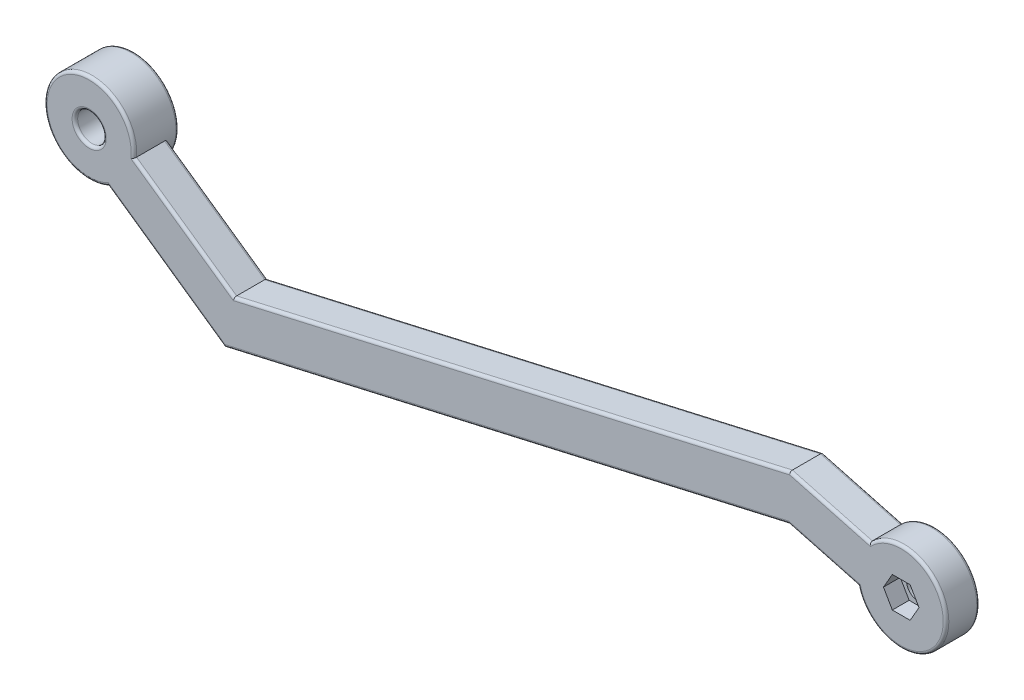
SolidWorks part; units mm, degrees
ref_plane "前视基准面" through (0, 0, 0) normal (0, 0, 1) x (1, 0, 0)
ref_plane "上视基准面" through (0, 0, 0) normal (0, 1, 0) x (1, 0, 0)
ref_plane "右视基准面" through (0, 0, 0) normal (1, 0, 0) x (0, 0, -1)
other "Configuration Table"
sketch "草图1" plane through (0, 0, 0) normal (0, 0, 1) x (1, 0, 0)
  line L0 (0, 0) -> (-145, 0) construction
  line L3 (-145, 0) -> (-120, -17.5052) construction
  line L4 (-120, -17.5052) -> (-20, 5.359) construction
  line L5 (-20, 5.359) -> (0, 0) construction
  line L7 (-142.7057, 3.2766) -> (-119.1604, -13.21)
  line L8 (-147.2943, -3.2766) -> (-120.8396, -21.8004)
  line L10 (-120.8396, -21.8004) -> (-20.0763, 1.2383)
  line L11 (-20.0763, 1.2383) -> (-1.0353, -3.8637)
  line L12 (1.0353, 3.8637) -> (-19.9237, 9.4796)
  line L13 (-19.9237, 9.4796) -> (-119.1604, -13.21)
  arc A0 (-5.6569, 5.6569) -> (-7.7274, -2.0706) centre (0, 0) cw
  arc A1 (-137.0304, -0.6972) -> (-141.6191, -7.2505) centre (-145, 0) ccw
  circle A2 centre (-145, 0) radius 4
  circle A3 centre (0, 0) radius 4
  circle A4 centre (-145, 0) radius 2.55
  circle A5 centre (0, 0) radius 2.05
  dimension "D2" = 8
  dimension "D3" = 8
  dimension "D6" = 5.1
  dimension "D7" = 4.1
  dimension "D1" = 145
  dimension "D4" = 25
  dimension "D5" = 35
  dimension "D8" = 15
  dimension "D9" = 20
  dimension "D10" = 4
  dimension "D11" = 4
extrude "凸台-拉伸1" add sketch "草图1" along normal mid plane 6 contours A2 A4 | A2 L7 A1 L8 | A3 L12 L13 L7 A2 L8 L10 L11 | A3 L11 A0 L12 | A3 A5 region at (-148.462, 2.4241, 0) region at (-74.4027, -5.6599, 0) region at (-141.5523, 1.7948, 0) region at (7.5107, -2.0125, 0) region at (3.0837, 2.3662, 0)
ref_axis "后基准轴" through (0, 0, 0) along (0, 0, 1)
ref_axis "前基准轴" through (-145, 0, 0) along (0, 0, 1)
sketch "草图2" plane through (0, 0, -3) normal (0, 0, 1) x (1, 0, 0)
  circle A0 centre (-145, 0) radius 2.55
  circle A1 centre (-145, 0) radius 8
  circle A2 centre (-145, 0) radius 2.55 construction
  arc A3 (-137.0304, -0.6972) -> (-141.6191, -7.2505) centre (-145, 0) ccw construction
extrude "凸台-拉伸2" add sketch "草图2" against normal blind 2 contours A1 A0 region at (-152.7737, 0, -3)
sketch "草图3" plane through (0, 0, 3) normal (0, 0, 1) x (1, 0, 0)
  line L1 (1.5877, -2.75) -> (3.1754, 0)
  line L2 (3.1754, 0) -> (1.5877, 2.75)
  line L3 (1.5877, 2.75) -> (-1.5877, 2.75)
  line L4 (-1.5877, 2.75) -> (-3.1754, 0)
  line L5 (-3.1754, 0) -> (-1.5877, -2.75)
  line L6 (-1.5877, -2.75) -> (1.5877, -2.75)
  circle A0 centre (0, 0) radius 2.75 construction
  dimension "D1" = 5.5
extrude "切除-拉伸1" cut sketch "草图3" against normal blind 3
fillet "圆角1" radius 0.5 19 edges at (-13.9018, -0.4161, -3) (-131.2293, -14.5254, -3) (-70.458, -10.281, -3) (-69.542, -1.8652, 3) (-128.0954, -6.9536, 3) (-131.2293, -14.5254, 3) (-153, 0, -5) (-128.0954, -6.9536, -3) (-69.542, -1.8652, -3) (7.7274, -2.0706, -3) (-12.7903, 7.5683, -3) (-12.7903, 7.5683, 3) (7.7274, -2.0706, 3) (-13.9018, -0.4161, 3) (-70.458, -10.281, 3) (2.05, 0, -3) (-147.55, 0, -5) (-142.45, 0, 3) (-151.5532, 4.5886, 3)
